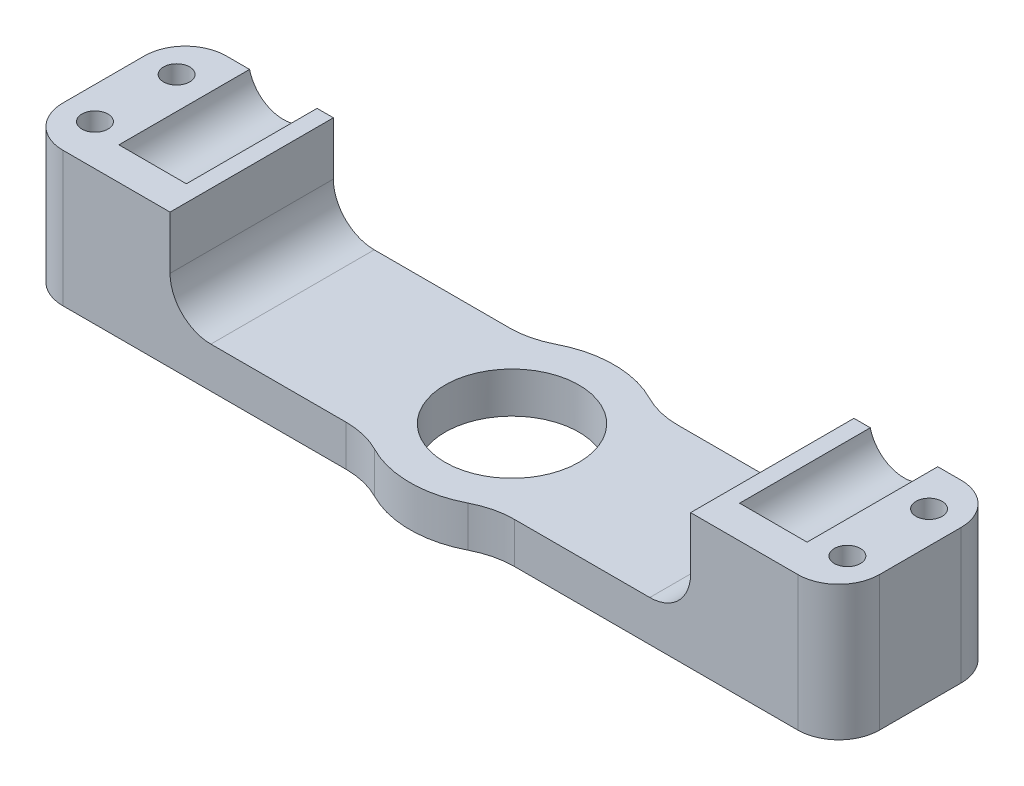
SolidWorks part; units mm, degrees
ref_plane "Front Plane" through (0, 0, 0) normal (0, 0, 1) x (1, 0, 0)
ref_plane "Top Plane" through (0, 0, 0) normal (0, 1, 0) x (1, 0, 0)
ref_plane "Right Plane" through (0, 0, 0) normal (1, 0, 0) x (0, 0, -1)
sketch "Sketch1" plane through (0, 0, 0) normal (0, 1, 0) x (1, 0, 0)
  line L0 (-44, 0) -> (-44, -44) construction
  line L1 (-44, -44) -> (44, -44) construction
  line L2 (44, -44) -> (44, 0) construction
  line L4 (-44, -10) -> (44, -10)
  line L5 (-44, -10) -> (-44, 10)
  line L6 (-44, 10) -> (44, 10)
  line L7 (44, -10) -> (44, 10)
  line L8 (-44, -10) -> (44, 10) construction
  line L9 (-44, 10) -> (44, -10) construction
  arc A0 (44, 0) -> (-44, 0) centre (0, 0) ccw construction
  dimension "D1" = 88
  dimension "D2" = 88
  dimension "D3" = 20
extrude "Boss-Extrude1" add sketch "Sketch1" along normal blind 35
sketch "Sketch2" plane through (0, 0, 10) normal (0, 0, 1) x (1, 0, 0)
  line L1 (-1044, 17.5) -> (48956, 17.5) construction
  line L2 (0, -1000) -> (0, 49000) construction
  line L3 (-44, 35) -> (-44, 0) construction
  circle A0 centre (-38, 17.5) radius 4.25
  circle A1 centre (38, 17.5) radius 4.25
  point P2 (-44, 17.5)
  dimension "D1" = 8.5
  dimension "D2" = 6
extrude "Cut-Extrude1" cut sketch "Sketch2" against normal through all
sketch "Sketch7" plane through (0, 35, 0) normal (0, 1, 0) x (1, 0, 0)
  circle A0 centre (0, 0) radius 12.5
  dimension "D1" = 25
extrude "Boss-Extrude2" add sketch "Sketch7" against normal up to surface (35 mm away) up to face at (0, 0, 0)
sketch "Sketch4" plane through (0, 35, 0) normal (0, 1, 0) x (1, 0, 0)
  circle A0 centre (0, 0) radius 8.2
  dimension "D1" = 16.4
extrude "Cut-Extrude3" cut sketch "Sketch4" against normal through all
fillet "Fillet2" radius 10 4 edges at (7.5, 17.5, 10) (-7.5, 17.5, 10) (7.5, 17.5, -10) (-7.5, 17.5, -10)
sketch "Sketch9" plane through (-44, 0, 0) normal (-1, 0, 0) x (0, 0, 1)
  line L5 (-1017.3065, 35) -> (48982.6935, 35) construction
  line L6 (-1016.9067, 16.5) -> (48983.0933, 16.5) construction
  line L7 (-12.5, 35) -> (-12.5, 0) construction
  line L8 (-10, 35) -> (10, 35) construction
  line L9 (12.5, 0) -> (12.5, 35) construction
  line L10 (-13.5, 35) -> (13.5, 35)
  line L11 (-13.5, 35) -> (-13.5, 16.5)
  line L12 (-13.5, 16.5) -> (13.5, 16.5)
  line L13 (13.5, 35) -> (13.5, 16.5)
  line L14 (-12.5, 35) -> (-12.5, 0) construction
  point P3 (-12.5, 16.5)
  point P21 (-12.5, 17.5)
  dimension "D1" = 1
  dimension "D2" = 1
  dimension "D3" = 1
extrude "Cut-Extrude4" cut sketch "Sketch9" against normal through all
sketch "Sketch10" plane through (0, 0, 0) normal (0, 0, 1) x (1, 0, 0)
  line L0 (44, 0) -> (10.3078, 0) construction
  line L1 (31.8693, 18.5) -> (-31.8693, 18.5)
  line L2 (31.8693, 18.5) -> (31.8693, 5)
  line L3 (31.8693, 5) -> (-31.8693, 5)
  line L4 (-31.8693, 18.5) -> (-31.8693, 5)
  line L5 (10.3078, 16.5) -> (33.8693, 16.5) construction
  dimension "D1" = 5
  dimension "D2" = 2
  dimension "D3" = 2
  dimension "D4" = 2
extrude "Cut-Extrude5" cut sketch "Sketch10" against normal through all and the other way through all
fillet "Fillet3" radius 5 2 edges at (-31.8693, 5, 0) (31.8693, 5, 0)
sketch "Sketch11" plane through (44, 0, 0) normal (1, 0, 0) x (0, 0, -1)
  line L4 (10, 0) -> (10, 16.5)
  line L5 (10, 16.5) -> (-10, 16.5)
  line L6 (-10, 16.5) -> (-10, 0)
  line L7 (-10, 0) -> (10, 0)
  line L8 (10, 0) -> (10, 16.5)
  line L9 (10, 16.5) -> (-10, 16.5)
  line L10 (-10, 16.5) -> (-10, 0)
  line L11 (-10, 0) -> (10, 0)
  dimension "D1" = 0
extrude "Boss-Extrude3" add sketch "Sketch11" along normal blind 6
sketch "Sketch12" plane through (0, 16.5, 0) normal (0, 1, 0) x (1, 0, 0)
  line L0 (50, -10) -> (42.1307, -10) construction
  line L1 (42.1307, 10) -> (50, 10) construction
  circle A0 centre (46.0653, 5) radius 1.6
  circle A1 centre (46.0653, -5) radius 1.6
  point P4 (46.0653, -10)
  dimension "D1" = 3.2
  dimension "D2" = 5
  dimension "D3" = 5
extrude "Cut-Extrude6" cut sketch "Sketch12" against normal through all
mirror "Mirror1" about plane through (0, 0, 0) normal (1, 0, 0) of "Cut-Extrude6", "Boss-Extrude3"
fillet "Fillet5" radius 5 4 edges at (-50, 8.25, -10) (-50, 8.25, 10) (50, 8.25, 10) (50, 8.25, -10)
sketch "Sketch13" plane through (0, 0, 10) normal (0, 0, 1) x (1, 0, 0)
  line L0 (-42.1307, 16.5) -> (-33.8693, 16.5)
  line L1 (33.8693, 16.5) -> (42.1307, 16.5)
  arc A0 (33.8693, 16.5) -> (42.1307, 16.5) centre (38, 17.5) ccw construction
  arc A1 (33.8693, 16.5) -> (42.1307, 16.5) centre (38, 17.5) ccw
  arc A2 (-42.1307, 16.5) -> (-33.8693, 16.5) centre (-38, 17.5) ccw construction
  arc A3 (-42.1307, 16.5) -> (-33.8693, 16.5) centre (-38, 17.5) ccw
extrude "Boss-Extrude4" add sketch "Sketch13" against normal blind 4
